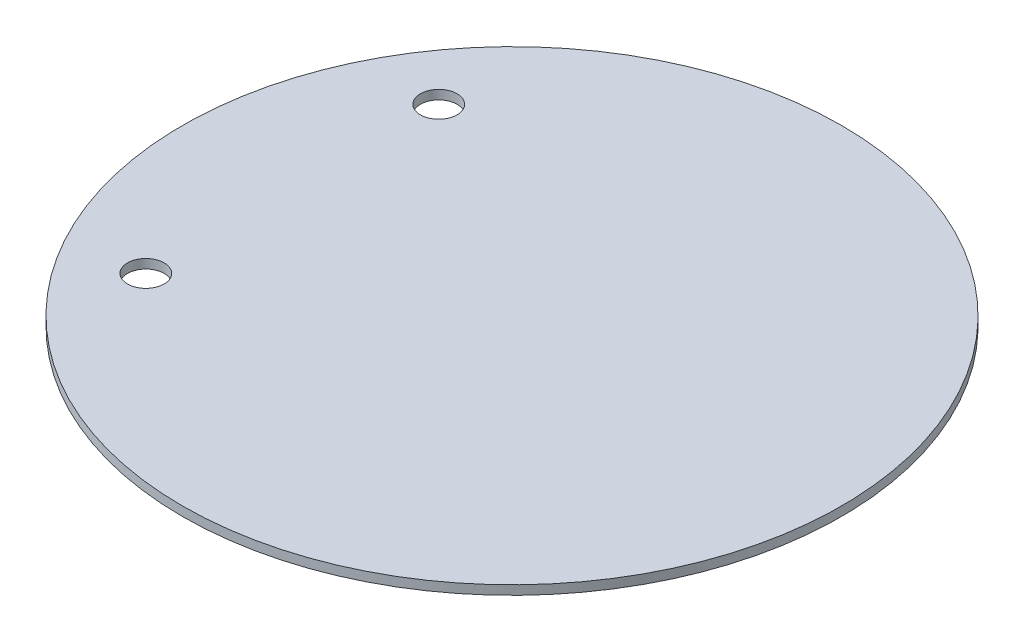
SolidWorks part; units mm, degrees
ref_plane "Front Plane" through (0, 0, 0) normal (0, 0, 1) x (1, 0, 0)
ref_plane "Top Plane" through (0, 0, 0) normal (0, 1, 0) x (1, 0, 0)
ref_plane "Right Plane" through (0, 0, 0) normal (1, 0, 0) x (0, 0, -1)
sketch "Sketch1" plane through (0, 0, 0) normal (0, 1, 0) x (1, 0, 0)
  line L0 (0, 0) -> (-122.0849, 0) construction
  line L1 (-38.1, 0) -> (-38.1, 25.4) construction
  circle A0 centre (0, 0) radius 57.15
  circle A2 centre (-38.1, 25.4) radius 3.175
  circle A3 centre (-38.1, -25.4) radius 3.175
  dimension "D1" = 114.3
  dimension "D4" = 6.35
  dimension "D2" = 50.8
  dimension "D3" = 38.1
extrude "Boss-Extrude1" add sketch "Sketch1" along normal blind 1.5875
